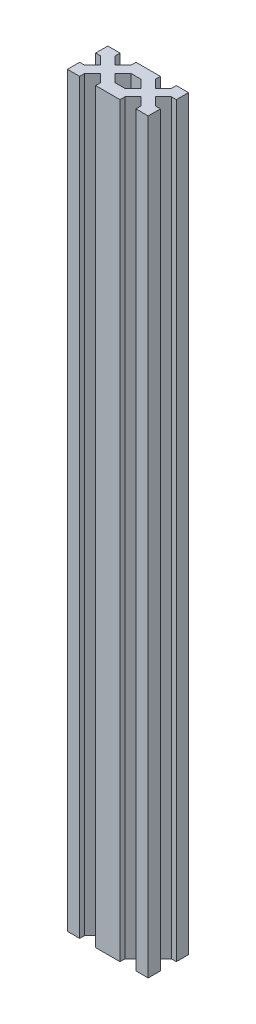
SolidWorks part; units mm, degrees
ref_plane "Plan de face" through (0, 0, 0) normal (0, 0, 1) x (1, 0, 0)
ref_plane "Plan de dessus" through (0, 0, 0) normal (0, 1, 0) x (1, 0, 0)
ref_plane "Plan de droite" through (0, 0, 0) normal (1, 0, 0) x (0, 0, -1)
sketch "Esquisse1" plane through (0, 0, 0) normal (0, 1, 0) x (1, 0, 0)
  line L0 (-2.5, 17.5) -> (-17.5, 17.5)
  line L1 (0, 0) -> (-20, 0)
  line L2 (0, 0) -> (0, 20)
  line L3 (0, 20) -> (-20, 20)
  line L4 (-20, 0) -> (-20, 20)
  line L5 (0, 20) -> (-20, 0) construction
  line L6 (-17.5, 2.5) -> (-17.5, 17.5)
  line L11 (-2.5, 2.5) -> (-17.5, 2.5)
  line L12 (-2.5, 2.5) -> (-2.5, 17.5)
  line L13 (-20, 20) -> (0, 0) construction
  line L14 (-26.9957, 23.4601) -> (-23.4601, 26.9957)
  line L15 (-26.9957, 23.4601) -> (3.4601, -6.9957)
  line L16 (-23.4601, 26.9957) -> (6.9957, -3.4601)
  line L17 (3.4601, -6.9957) -> (6.9957, -3.4601)
  line L18 (-26.9957, 23.4601) -> (6.9957, -3.4601) construction
  line L19 (-23.4601, 26.9957) -> (3.4601, -6.9957) construction
  line L20 (-10, 20) -> (-10, 0) construction
  line L21 (-23.4601, -6.9957) -> (-26.9957, -3.4601)
  line L22 (3.4601, 26.9957) -> (-26.9957, -3.4601)
  line L23 (6.9957, 23.4601) -> (-23.4601, -6.9957)
  line L24 (6.9957, 23.4601) -> (3.4601, 26.9957)
  line L25 (-17.5, 13.9645) -> (-20, 13.9645)
  line L26 (-20, 10) -> (20, 10) construction
  line L27 (-17.5, 6.0355) -> (-20, 6.0355)
  line L28 (-2.5, 6.0355) -> (2.5, 6.0355)
  line L29 (-2.5, 13.9645) -> (2.5, 13.9645)
  line L30 (-2.5, 6.0355) -> (2.5, 6.0355)
  line L31 (-2.5, 13.9645) -> (2.5, 13.9645)
  line L32 (-13.9645, 2.5) -> (-13.9645, 0)
  line L33 (-6.0355, 17.5) -> (-6.0355, 20)
  line L34 (-13.9645, 17.5) -> (-13.9645, 20)
  line L35 (-6.0355, 2.5) -> (-6.0355, 0)
  line L36 (0, 20) -> (0, -49980) construction
  line L37 (6.0355, 2.5) -> (6.0355, 0)
  line L38 (13.9645, 2.5) -> (13.9645, 0)
  line L39 (10, 20) -> (10, 0) construction
  line L40 (23.4601, 26.9957) -> (-3.4601, -6.9957) construction
  line L41 (26.9957, 23.4601) -> (-6.9957, -3.4601) construction
  line L42 (20, 20) -> (0, 0) construction
  line L43 (0, 20) -> (20, 0) construction
  line L44 (13.9645, 17.5) -> (13.9645, 20)
  line L45 (6.0355, 17.5) -> (6.0355, 20)
  line L46 (17.5, 6.0355) -> (20, 6.0355)
  line L47 (17.5, 13.9645) -> (20, 13.9645)
  line L48 (-6.9957, 23.4601) -> (-3.4601, 26.9957)
  line L49 (-6.9957, 23.4601) -> (23.4601, -6.9957)
  line L50 (-3.4601, 26.9957) -> (26.9957, -3.4601)
  line L51 (23.4601, -6.9957) -> (26.9957, -3.4601)
  line L52 (-3.4601, -6.9957) -> (-6.9957, -3.4601)
  line L53 (23.4601, 26.9957) -> (-6.9957, -3.4601)
  line L54 (26.9957, 23.4601) -> (-3.4601, -6.9957)
  line L55 (26.9957, 23.4601) -> (23.4601, 26.9957)
  line L56 (2.5, 2.5) -> (2.5, 17.5)
  line L57 (2.5, 2.5) -> (17.5, 2.5)
  line L58 (17.5, 2.5) -> (17.5, 17.5)
  line L59 (20, 0) -> (20, 20)
  line L60 (0, 20) -> (20, 20)
  line L61 (0, 0) -> (0, 20)
  line L62 (0, 0) -> (20, 0)
  line L63 (2.5, 17.5) -> (17.5, 17.5)
  point P11 (-10, 10)
  point P44 (0, 6.0355)
  point P45 (0, 10)
  point P59 (0, 13.9645)
  point P68 (10, 10)
  dimension "D1" = 20
  dimension "D2" = 20
  dimension "D3" = 7.3934
  dimension "D4" = 2.5
  dimension "D5" = 43.071
  dimension "D6" = 2.5
extrude "Boss.-Extru.1" [suppressed] add sketch "Esquisse1" along normal blind 340 contours L15 L35 L1 | L16 L12 L11 L15 L1 L2 | L28 L16 L2 | L16 L23 L15 L11 L12 | L32 L23 L1 | L23 L11 L6 L22 L4 L1 | L22 L27 L4 | L23 L15 L22 L6 L11 | L23 L16 L22 L15 | L23 L12 L0 L22 L16 | L23 L2 L3 L22 L0 L12 | L23 L29 L2 | L33 L22 L3 | L16 L34 L3 | L16 L3 L4 L15 L6 L0 | L25 L15 L4 | L22 L16 L0 L6 L15
extrude "Boss.-Extru.2" add sketch "Esquisse1<3>" along normal blind 370 contours L49 L62 L59 L50 L58 L57 | L38 L62 L49 | L50 L59 L46 | L60 L44 L53 | L47 L59 L54 | L53 L63 L58 L54 L59 L60 | L57 L58 L50 L54 L49 | L54 L50 L53 L49 | L63 L53 L50 L54 L58 | L56 L57 L54 L49 L53 | L57 L56 L53 L16 L54 | L2 L62 L16 | L2 L53 L1 | L53 L16 L12 L11 L15 | L28 L16 L2 | L53 L28 L2 | L15 L35 L1 | L54 L62 L37 | L16 L23 L15 L11 L12 | L23 L29 L2 | L49 L2 L29 | L56 L63 L50 L23 L49 | L60 L50 L45 | L60 L2 L23 | L49 L22 L0 L12 L23 | L3 L49 L2 | L33 L22 L3 | L23 L12 L0 L22 L16 | L23 L16 L22 L15 | L16 L34 L3 | L16 L3 L4 L15 L6 L0 | L25 L15 L4 | L22 L16 L0 L6 L15 | L22 L27 L4 | L32 L23 L1 | L23 L11 L6 L22 L4 L1 | L23 L15 L22 L6 L11 | L63 L56 L49 L53 L50 region at (-5.7812, 0, -14.2188) region at (-4.2678, 0, -17.5854) region at (-5.2022, 0, -19.1667) region at (-0.8333, 0, -14.7978) region at (-14.2188, 0, -14.2188) region at (-17.8661, 0, -17.8661) region at (-14.7978, 0, -19.1667) region at (-1.1785, 0, -18.8215) region at (-10, 0, -10) region at (-1.3104, 0, -4.7252) region at (-5.7812, 0, -5.7812) region at (-0.8333, 0, -5.2022) region at (0.8333, 0, -14.7978) region at (1.1785, 0, -18.8215) region at (1.8281, 0, -18.1719) region at (-14.2188, 0, -5.7812) region at (1.1785, 0, -1.1785) region at (1.3104, 0, -4.7252) region at (0.8333, 0, -5.2022) region at (-1.1785, 0, -1.1785) region at (5.2022, 0, -19.1667) region at (5.7812, 0, -14.2188) region at (-19.1667, 0, -14.7978) region at (-17.8661, 0, -2.1339) region at (-19.1667, 0, -5.2022) region at (-5.2022, 0, -0.8333) region at (5.2022, 0, -0.8333) region at (5.7812, 0, -5.7812) region at (10, 0, -10) region at (-14.7978, 0, -0.8333) region at (14.2188, 0, -14.2188) region at (14.7978, 0, -19.1667) region at (17.8661, 0, -17.8661) region at (14.2188, 0, -5.7812) region at (14.7978, 0, -0.8333) region at (17.8661, 0, -2.1339) region at (19.1667, 0, -5.2022) region at (19.1667, 0, -14.7978)
sketch "Esquisse1<3>" plane through (0, 0, 0) normal (0, 1, 0) x (1, 0, 0) same geometry as "Esquisse1"
sketch "Esquisse2" plane through (0, 0, -20) normal (0, 0, -1) x (-1, 0, 0)
  line L0 (20, 370) -> (20, 358)
  line L1 (20, 370) -> (-10, 370)
  line L2 (20, 358) -> (-10, 358)
  line L3 (-10, 370) -> (-10, 358)
  line L4 (20, 370) -> (20, 0) construction
  circle A0 centre (-10, 358) radius 9.1834
  dimension "D3" = 18.3669
  dimension "D1" = 30
  dimension "D2" = 12
